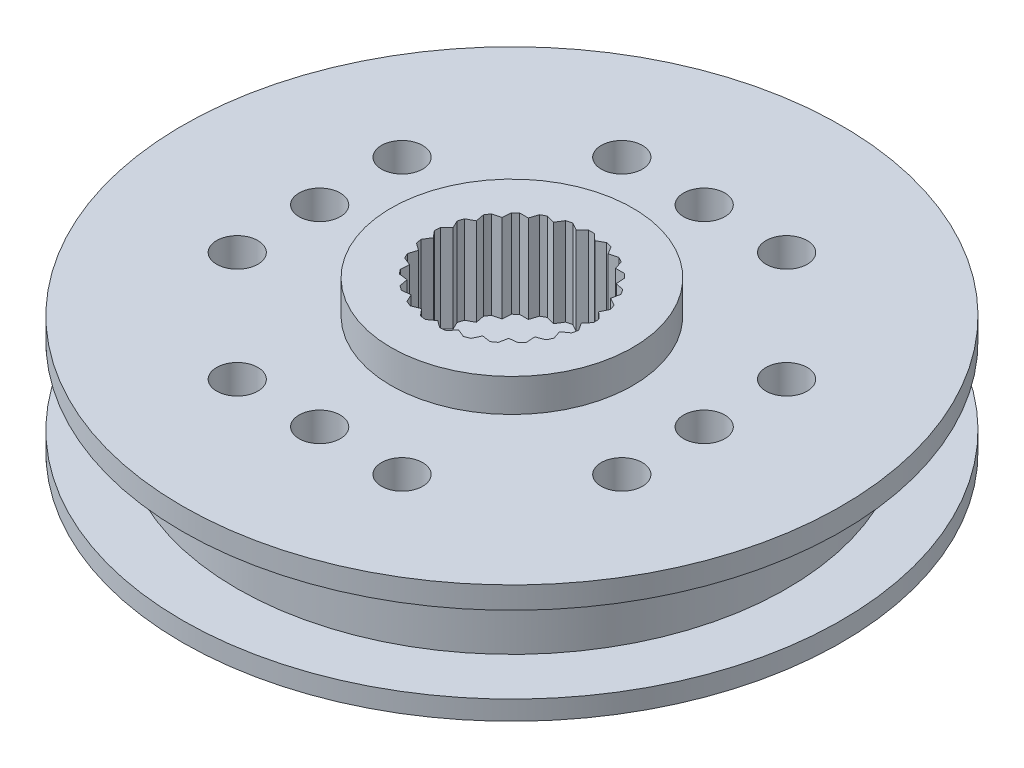
SolidWorks part; units mm, degrees
material "ABS"
ref_plane "Front Plane" through (0, 0, 0) normal (0, 0, 1) x (1, 0, 0)
ref_plane "Top Plane" through (0, 0, 0) normal (0, 1, 0) x (1, 0, 0)
ref_plane "Right Plane" through (0, 0, 0) normal (1, 0, 0) x (0, 0, -1)
sketch "Sketch2" plane through (0, 0, 0) normal (0, 1, 0) x (1, 0, 0)
  circle A0 centre (0, 0) radius 6
  circle A1 centre (0, 0) radius 1.5
  dimension "D1" = 12
  dimension "D2" = 3
extrude "Boss-Extrude1" add sketch "Sketch2" along normal mid plane 2.3
sketch "Sketch3" plane through (0, 1.15, 0) normal (0, 1, 0) x (1, 0, 0)
  line L0 (0, 0) -> (0, 2.9) construction
  line L3 (0, 0) -> (0.376, 2.9763) construction
  line L52 (0.1074, 2.898) -> (0.3384, 2.6787)
  line L53 (-0.1074, 2.898) -> (-0.3384, 2.6787)
  line L54 (0.8248, 2.7802) -> (0.9939, 2.5104)
  line L55 (0.6167, 2.8337) -> (0.3384, 2.6787)
  line L56 (1.4903, 2.4878) -> (1.587, 2.1843)
  line L57 (1.302, 2.5913) -> (0.9939, 2.5104)
  line L58 (2.0621, 2.039) -> (2.0804, 1.721)
  line L59 (1.9055, 2.1861) -> (1.587, 2.1843)
  line L60 (2.5044, 1.4621) -> (2.443, 1.1496)
  line L61 (2.3893, 1.6435) -> (2.0804, 1.721)
  line L62 (2.7894, 0.7934) -> (2.6522, 0.5059)
  line L63 (2.723, 0.9977) -> (2.443, 1.1496)
  line L64 (2.899, 0.0748) -> (2.6947, -0.1695)
  line L65 (2.8855, 0.2892) -> (2.6522, 0.5059)
  line L66 (2.8265, -0.6486) -> (2.5679, -0.8343)
  line L67 (2.8668, -0.4375) -> (2.6947, -0.1695)
  line L68 (2.5765, -1.3311) -> (2.2797, -1.4467)
  line L69 (2.6679, -1.1367) -> (2.5679, -0.8343)
  line L70 (2.1645, -1.93) -> (1.8483, -1.9682)
  line L71 (2.3014, -1.7645) -> (2.2797, -1.4467)
  line L72 (1.6165, -2.4077) -> (1.3007, -2.366)
  line L73 (1.7903, -2.2814) -> (1.8483, -1.9682)
  line L74 (0.967, -2.734) -> (0.6715, -2.6152)
  line L75 (1.1667, -2.655) -> (1.3007, -2.366)
  line L76 (0.2566, -2.8886) -> (0, -2.7)
  line L77 (0.4698, -2.8617) -> (0.6715, -2.6152)
  line L78 (-0.4698, -2.8617) -> (-0.6715, -2.6152)
  line L79 (-0.2566, -2.8886) -> (0, -2.7)
  line L80 (-1.1667, -2.655) -> (-1.3007, -2.366)
  line L81 (-0.967, -2.734) -> (-0.6715, -2.6152)
  line L82 (-1.7903, -2.2814) -> (-1.8483, -1.9682)
  line L83 (-1.6165, -2.4077) -> (-1.3007, -2.366)
  line L84 (-2.3014, -1.7645) -> (-2.2797, -1.4467)
  line L85 (-2.1645, -1.93) -> (-1.8483, -1.9682)
  line L86 (-2.6679, -1.1367) -> (-2.5679, -0.8343)
  line L87 (-2.5765, -1.3311) -> (-2.2797, -1.4467)
  line L88 (-2.8668, -0.4375) -> (-2.6947, -0.1695)
  line L89 (-2.8265, -0.6486) -> (-2.5679, -0.8343)
  line L90 (-2.8855, 0.2892) -> (-2.6522, 0.5059)
  line L91 (-2.899, 0.0748) -> (-2.6947, -0.1695)
  line L92 (-2.723, 0.9977) -> (-2.443, 1.1496)
  line L93 (-2.7894, 0.7934) -> (-2.6522, 0.5059)
  line L94 (-2.3893, 1.6435) -> (-2.0804, 1.721)
  line L95 (-2.5044, 1.4621) -> (-2.443, 1.1496)
  line L96 (-1.9055, 2.1861) -> (-1.587, 2.1843)
  line L97 (-2.0621, 2.039) -> (-2.0804, 1.721)
  line L98 (-1.302, 2.5913) -> (-0.9939, 2.5104)
  line L99 (-1.4903, 2.4878) -> (-1.587, 2.1843)
  line L100 (-0.6167, 2.8337) -> (-0.3384, 2.6787)
  line L101 (-0.8248, 2.7802) -> (-0.9939, 2.5104)
  line L102 (-2.533, 1.6075) -> (-2.3893, 1.6435) construction
  line L103 (-2.533, 1.6075) -> (-2.5044, 1.4621) construction
  line L104 (-2.8532, 0.9271) -> (-2.723, 0.9977) construction
  line L105 (-2.8532, 0.9271) -> (-2.7894, 0.7934) construction
  line L106 (-2.9941, 0.1884) -> (-2.8855, 0.2892) construction
  line L107 (-2.9941, 0.1884) -> (-2.899, 0.0748) construction
  line L108 (-2.9469, -0.5621) -> (-2.8668, -0.4375) construction
  line L109 (-2.9469, -0.5621) -> (-2.8265, -0.6486) construction
  line L110 (0, 3) -> (0.1074, 2.898) construction
  line L111 (0, 2.9) -> (0, 3) construction
  line L112 (0, 3) -> (-0.1074, 2.898) construction
  line L113 (-0.7461, 2.9057) -> (-0.6167, 2.8337) construction
  line L114 (-0.7461, 2.9057) -> (-0.8248, 2.7802) construction
  line L115 (-1.4453, 2.6289) -> (-1.302, 2.5913) construction
  line L116 (-1.4453, 2.6289) -> (-1.4903, 2.4878) construction
  line L117 (-2.0536, 2.1869) -> (-1.9055, 2.1861) construction
  line L118 (-2.0536, 2.1869) -> (-2.0621, 2.039) construction
  line L119 (-2.7145, -1.2773) -> (-2.6679, -1.1367) construction
  line L120 (-2.7145, -1.2773) -> (-2.5765, -1.3311) construction
  line L121 (-2.3115, -1.9123) -> (-2.3014, -1.7645) construction
  line L122 (-2.3115, -1.9123) -> (-2.1645, -1.93) construction
  line L123 (-1.7634, -2.4271) -> (-1.7903, -2.2814) construction
  line L124 (-1.7634, -2.4271) -> (-1.6165, -2.4077) construction
  line L125 (-1.1044, -2.7893) -> (-1.1667, -2.655) construction
  line L126 (-1.1044, -2.7893) -> (-0.967, -2.734) construction
  line L127 (-0.376, -2.9763) -> (-0.4698, -2.8617) construction
  line L128 (-0.376, -2.9763) -> (-0.2566, -2.8886) construction
  line L129 (0.376, -2.9763) -> (0.2566, -2.8886) construction
  line L130 (0.376, -2.9763) -> (0.4698, -2.8617) construction
  line L131 (1.1044, -2.7893) -> (0.967, -2.734) construction
  line L132 (1.1044, -2.7893) -> (1.1667, -2.655) construction
  line L133 (1.7634, -2.4271) -> (1.6165, -2.4077) construction
  line L134 (1.7634, -2.4271) -> (1.7903, -2.2814) construction
  line L135 (2.3115, -1.9123) -> (2.3014, -1.7645) construction
  line L136 (2.3115, -1.9123) -> (2.1645, -1.93) construction
  line L137 (2.7145, -1.2773) -> (2.6679, -1.1367) construction
  line L138 (2.7145, -1.2773) -> (2.5765, -1.3311) construction
  line L139 (2.9469, -0.5621) -> (2.8668, -0.4375) construction
  line L140 (2.9469, -0.5621) -> (2.8265, -0.6486) construction
  line L141 (2.9941, 0.1884) -> (2.8855, 0.2892) construction
  line L142 (2.9941, 0.1884) -> (2.899, 0.0748) construction
  line L143 (2.8532, 0.9271) -> (2.723, 0.9977) construction
  line L144 (2.8532, 0.9271) -> (2.7894, 0.7934) construction
  line L145 (2.533, 1.6075) -> (2.3893, 1.6435) construction
  line L146 (2.533, 1.6075) -> (2.5044, 1.4621) construction
  line L147 (2.0536, 2.1869) -> (1.9055, 2.1861) construction
  line L148 (2.0536, 2.1869) -> (2.0621, 2.039) construction
  line L149 (1.4453, 2.6289) -> (1.302, 2.5913) construction
  line L150 (1.4453, 2.6289) -> (1.4903, 2.4878) construction
  line L151 (0.7461, 2.9057) -> (0.6167, 2.8337) construction
  line L152 (0.7461, 2.9057) -> (0.8248, 2.7802) construction
  circle A0 centre (0, 0) radius 4.4
  circle A1 centre (0, 0) radius 3 construction
  circle A2 centre (0, 0) radius 2.7 construction
  arc A3 (-0.6167, 2.8337) -> (-0.8248, 2.7802) centre (0, 0) ccw
  arc A4 (-0.1074, 2.898) -> (-0.6167, 2.8337) centre (0, 0) ccw construction
  arc A5 (-0.8248, 2.7802) -> (-1.302, 2.5913) centre (0, 0) ccw construction
  arc A6 (-1.302, 2.5913) -> (-1.4903, 2.4878) centre (0, 0) ccw
  arc A7 (-1.4903, 2.4878) -> (-1.9055, 2.1861) centre (0, 0) ccw construction
  arc A8 (-1.9055, 2.1861) -> (-2.0621, 2.039) centre (0, 0) ccw
  arc A9 (-2.0621, 2.039) -> (-2.3893, 1.6435) centre (0, 0) ccw construction
  arc A10 (-2.3893, 1.6435) -> (-2.5044, 1.4621) centre (0, 0) ccw
  arc A11 (-2.5044, 1.4621) -> (-2.723, 0.9977) centre (0, 0) ccw construction
  arc A12 (-2.723, 0.9977) -> (-2.7894, 0.7934) centre (0, 0) ccw
  arc A13 (-2.7894, 0.7934) -> (-2.8855, 0.2892) centre (0, 0) ccw construction
  arc A14 (-2.8855, 0.2892) -> (-2.899, 0.0748) centre (0, 0) ccw
  arc A15 (-2.899, 0.0748) -> (-2.8668, -0.4375) centre (0, 0) ccw construction
  arc A16 (-2.8668, -0.4375) -> (-2.8265, -0.6486) centre (0, 0) ccw
  arc A17 (-2.8265, -0.6486) -> (-2.6679, -1.1367) centre (0, 0) ccw construction
  arc A18 (-2.6679, -1.1367) -> (-2.5765, -1.3311) centre (0, 0) ccw
  arc A19 (-2.5765, -1.3311) -> (-2.3014, -1.7645) centre (0, 0) ccw construction
  arc A20 (-2.3014, -1.7645) -> (-2.1645, -1.93) centre (0, 0) ccw
  arc A21 (-2.1645, -1.93) -> (-1.7903, -2.2814) centre (0, 0) ccw construction
  arc A22 (-1.7903, -2.2814) -> (-1.6165, -2.4077) centre (0, 0) ccw
  arc A23 (-1.6165, -2.4077) -> (-1.1667, -2.655) centre (0, 0) ccw construction
  arc A24 (-1.1667, -2.655) -> (-0.967, -2.734) centre (0, 0) ccw
  arc A25 (-0.967, -2.734) -> (-0.4698, -2.8617) centre (0, 0) ccw construction
  arc A26 (-0.4698, -2.8617) -> (-0.2566, -2.8886) centre (0, 0) ccw
  arc A27 (-0.2566, -2.8886) -> (0.2566, -2.8886) centre (0, 0) ccw construction
  arc A28 (0.2566, -2.8886) -> (0.4698, -2.8617) centre (0, 0) ccw
  arc A29 (0.4698, -2.8617) -> (0.967, -2.734) centre (0, 0) ccw construction
  arc A30 (0.967, -2.734) -> (1.1667, -2.655) centre (0, 0) ccw
  arc A31 (1.1667, -2.655) -> (1.6165, -2.4077) centre (0, 0) ccw construction
  arc A32 (1.6165, -2.4077) -> (1.7903, -2.2814) centre (0, 0) ccw
  arc A33 (1.7903, -2.2814) -> (2.1645, -1.93) centre (0, 0) ccw construction
  arc A34 (2.1645, -1.93) -> (2.3014, -1.7645) centre (0, 0) ccw
  arc A35 (2.3014, -1.7645) -> (2.5765, -1.3311) centre (0, 0) ccw construction
  arc A36 (2.5765, -1.3311) -> (2.6679, -1.1367) centre (0, 0) ccw
  arc A37 (2.6679, -1.1367) -> (2.8265, -0.6486) centre (0, 0) ccw construction
  arc A38 (2.8265, -0.6486) -> (2.8668, -0.4375) centre (0, 0) ccw
  arc A39 (2.8668, -0.4375) -> (2.899, 0.0748) centre (0, 0) ccw construction
  arc A40 (2.899, 0.0748) -> (2.8855, 0.2892) centre (0, 0) ccw
  arc A41 (2.8855, 0.2892) -> (2.7894, 0.7934) centre (0, 0) ccw construction
  arc A42 (2.7894, 0.7934) -> (2.723, 0.9977) centre (0, 0) ccw
  arc A43 (2.723, 0.9977) -> (2.5044, 1.4621) centre (0, 0) ccw construction
  arc A44 (2.5044, 1.4621) -> (2.3893, 1.6435) centre (0, 0) ccw
  arc A45 (2.3893, 1.6435) -> (2.0621, 2.039) centre (0, 0) ccw construction
  arc A46 (2.0621, 2.039) -> (1.9055, 2.1861) centre (0, 0) ccw
  arc A47 (1.9055, 2.1861) -> (1.4903, 2.4878) centre (0, 0) ccw construction
  arc A48 (1.4903, 2.4878) -> (1.302, 2.5913) centre (0, 0) ccw
  arc A49 (1.302, 2.5913) -> (0.8248, 2.7802) centre (0, 0) ccw construction
  arc A50 (0.8248, 2.7802) -> (0.6167, 2.8337) centre (0, 0) ccw
  arc A51 (0.3635, 2.8771) -> (0.1074, 2.898) centre (0, 0) ccw construction
  arc A52 (0.1074, 2.898) -> (-0.1074, 2.898) centre (0, 0) ccw
  arc A53 (0.6167, 2.8337) -> (0.3635, 2.8771) centre (0, 0) ccw construction
  point P84 (0, 0)
  dimension "D1" = 8.8
  dimension "D2" = 5.4
  dimension "D3" = 6
  dimension "D6" = 5.8
  dimension "D4" = 7.2
  dimension "D5" = 25
extrude "Boss-Extrude2" add sketch "Sketch3" along normal blind 3.2
sketch "Sketch4" plane through (0, 0, 0) normal (0, 1, 0) x (1, 0, 0)
  line L0 (0, 0) -> (13, 0) construction
  line L1 (3.9686, 4.5) -> (14.0007, 2.4494)
  line L2 (3.9686, -4.5) -> (14.0007, -2.4494)
  line L3 (13, 0) -> (10, 0) construction
  circle A0 centre (0, 0) radius 6 construction
  arc A1 (3.9686, -4.5) -> (3.9686, 4.5) centre (0, 0) ccw
  arc A2 (14.0007, 2.4494) -> (14.0007, -2.4494) centre (13.5, 0) cw
  circle A3 centre (13, 0) radius 0.75
  circle A4 centre (10, 0) radius 0.75
  circle A5 centre (7, 0) radius 0.75
  dimension "D3" = 2.5
  dimension "D5" = 1.5
  dimension "D2" = 9
  dimension "D7" = 3
  dimension "D4" = 0.5
  dimension "D1" = 13
  dimension "D6" = 3
extrude "Boss-Extrude3" [suppressed] add sketch "Sketch4" along normal mid plane 2.3
pattern_circular "CirPattern1" [suppressed] count 6 over 360 of bodies 103
sketch "Sketch5" plane through (0, 0, 0) normal (0, 1, 0) x (1, 0, 0)
  line L0 (3, 7) -> (-3, 7) construction
  circle A0 centre (0, 0) radius 10
  circle A1 centre (0, 7) radius 0.75
  circle A2 centre (-3, 7) radius 0.75
  circle A3 centre (3, 7) radius 0.75
  circle A4 centre (7, 3) radius 0.75
  circle A5 centre (7, 0) radius 0.75
  circle A6 centre (7, -3) radius 0.75
  circle A7 centre (3, -7) radius 0.75
  circle A8 centre (0, -7) radius 0.75
  circle A9 centre (-3, -7) radius 0.75
  circle A10 centre (-7, -3) radius 0.75
  circle A11 centre (-7, 0) radius 0.75
  circle A12 centre (-7, 3) radius 0.75
  circle A13 centre (0, 0) radius 1.5 construction
  circle A14 centre (0, 0) radius 1.5
  point P8 (0, 7)
  point P31 (0, 0)
  dimension "D1" = 1.5
  dimension "D3" = 2.25
  dimension "D4" = 6
  dimension "D2" = 7
  dimension "D5" = 4
extrude "Boss-Extrude4" add sketch "Sketch5" along normal mid plane 2.3
sketch "Esquisse3" plane through (0, 1.15, 0) normal (0, 1, 0) x (1, 0, 0)
  line L0 (0, 0) -> (0, 8.3761) construction
  line L1 (0, 0) -> (13.6065, 0) construction
  line L2 (-3.025, 0) -> (3.025, 0) construction
ref_plane "Plan1" through (0, 1.15, 0) normal (0, 1, 0) x (1, 0, 0)
sketch "Esquisse4" plane through (0, 1.15, 0) normal (0, 1, 0) x (1, 0, 0)
  circle A0 centre (0, 0) radius 10
  circle A1 centre (0, 0) radius 9
extrude "Enlèv. mat.-Extru.1" cut sketch "Esquisse4" against normal blind 1 from offset 0.6 offset against normal yes
sketch "Esquisse5" plane through (0, 1.15, 0) normal (0, 1, 0) x (1, 0, 0)
  circle A0 centre (0, 0) radius 11.9986
  circle A1 centre (0, 0) radius 10 construction
  circle A2 centre (0, 0) radius 10
extrude "Boss.-Extru.1" add sketch "Esquisse5" against normal blind 0.55
extrude "Boss.-Extru.2" add sketch "Esquisse5<3>" against normal blind 0.7 from offset 1.6 offset against normal yes
sketch "Esquisse5<3>" plane through (0, 1.15, 0) normal (0, 1, 0) x (1, 0, 0) same geometry as "Esquisse5"
extrude "Boss.-Extru.3" add sketch "Esquisse5<4>" against normal blind 0.6
sketch "Esquisse5<4>" plane through (0, 1.15, 0) normal (0, 1, 0) x (1, 0, 0) same geometry as "Esquisse5"
sketch "Esquisse6" plane through (0, 1.15, 0) normal (0, 1, 0) x (1, 0, 0)
  circle A0 centre (0, 0) radius 11
  circle A1 centre (0, 0) radius 9.7947
extrude "Boss.-Extru.4" add sketch "Esquisse6" against normal blind 1.6
sketch "Esquisse7" plane through (0, 1.15, 0) normal (0, 1, 0) x (1, 0, 0)
  circle A0 centre (0, 0) radius 11.9986 construction
  circle A1 centre (0, 0) radius 11.9986
  circle A2 centre (0, 0) radius 4.4 construction
  circle A3 centre (0, 0) radius 4.4
extrude "Boss.-Extru.5" add sketch "Esquisse7" along normal blind 2
sketch "Esquisse8" plane through (0, 1.15, 0) normal (0, 1, 0) x (1, 0, 0)
  circle A0 centre (0, 0) radius 11 construction
  circle A1 centre (0, 0) radius 11
  circle A2 centre (0, 0) radius 11.9986 construction
  circle A3 centre (0, 0) radius 11.9986
extrude "Enlèv. mat.-Extru.2" cut sketch "Esquisse8" along normal blind 2.2 from offset 1 offset against normal yes
ref_plane "Plan2" through (0, -1.15, 0) normal (0, -1, 0) x (-1, 0, 0)
sketch "Esquisse9" plane through (0, -1.15, 0) normal (0, -1, 0) x (-1, 0, 0)
  line L0 (0, 0) -> (0, 12.8461) construction
  line L1 (0, 0) -> (16.2753, 0) construction
  circle A0 centre (3, 7) radius 0.75 construction
  circle A1 centre (3, 7) radius 0.75
  circle A2 centre (7, 3) radius 0.75 construction
  circle A3 centre (7, 0) radius 0.75 construction
  circle A4 centre (7, -3) radius 0.75 construction
  circle A5 centre (3, -7) radius 0.75 construction
  circle A6 centre (0, -7) radius 0.75 construction
  circle A7 centre (-3, -7) radius 0.75 construction
  circle A8 centre (-7, -3) radius 0.75 construction
  circle A9 centre (-7, 0) radius 0.75 construction
  circle A10 centre (-7, 3) radius 0.75 construction
  circle A11 centre (-3, 7) radius 0.75 construction
  circle A12 centre (0, 7) radius 0.75 construction
  circle A13 centre (7, 3) radius 0.75
  circle A14 centre (7, 0) radius 0.75
  circle A15 centre (7, -3) radius 0.75
  circle A16 centre (3, -7) radius 0.75
  circle A17 centre (0, -7) radius 0.75
  circle A18 centre (-3, -7) radius 0.75
  circle A19 centre (-7, -3) radius 0.75
  circle A20 centre (-7, 0) radius 0.75
  circle A21 centre (-7, 3) radius 0.75
  circle A22 centre (-3, 7) radius 0.75
  circle A23 centre (0, 7) radius 0.75
extrude "Enlèv. mat.-Extru.3" cut sketch "Esquisse9" against normal blind 32.2 from offset 10
sketch "Esquisse10" plane through (0, 1.15, 0) normal (0, 1, 0) x (1, 0, 0)
  line L0 (0, 0) -> (0, 10.1685) construction
  circle A0 centre (0, 0) radius 11.9986 construction
  circle A1 centre (0, 0) radius 11.9986
  circle A2 centre (0, 0) radius 10.0052
extrude "Enlèv. mat.-Extru.4" cut sketch "Esquisse10" against normal blind 2.8 from offset 1.2
equation "\"N_hole\"= 3"
equation "\"N_horn\"= 6"
equation "\"D6@Sketch4\"=\"N_hole\""
equation "\"D1@CirPattern1\"=\"N_horn\""
equation "\"D1@Sketch4\"=(\"N_hole\" - 1) *3 +7"
